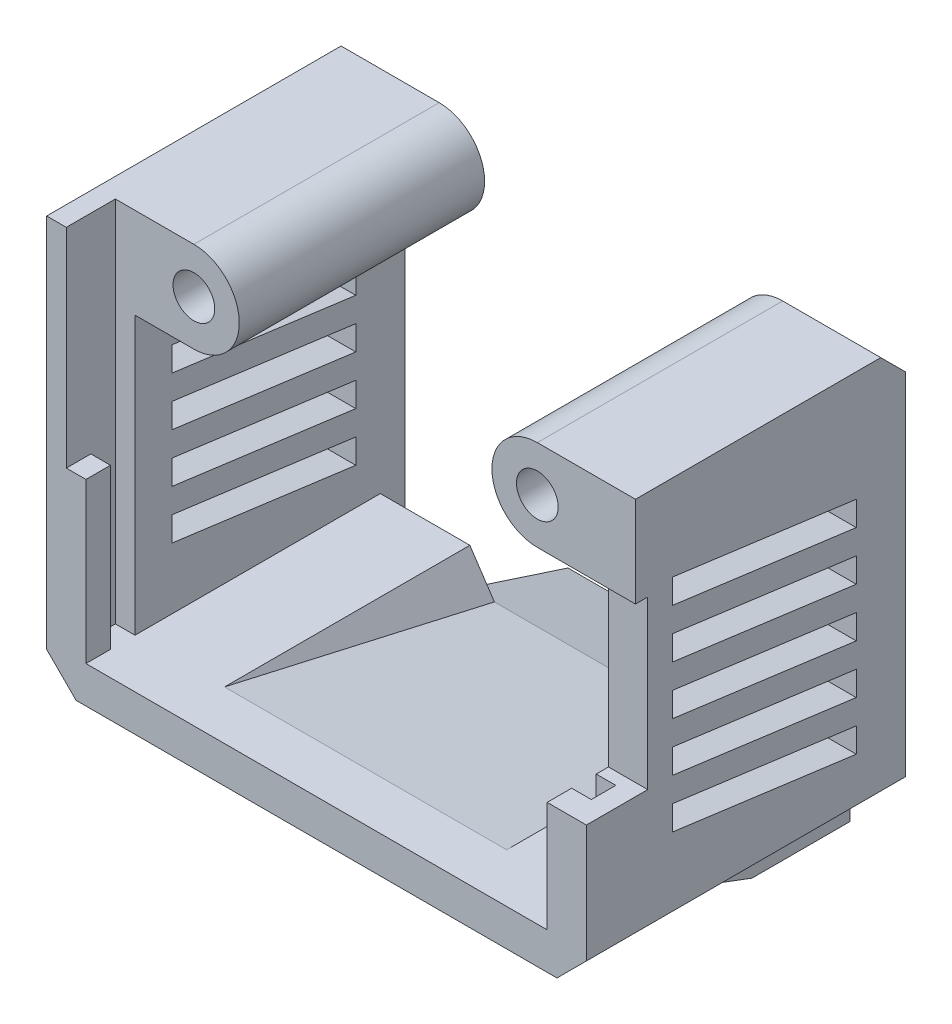
SolidWorks part; units mm, degrees
ref_plane "Спереди" through (0, 0, 0) normal (0, 0, 1) x (1, 0, 0)
ref_plane "Сверху" through (0, 0, 0) normal (0, 1, 0) x (1, 0, 0)
ref_plane "Справа" through (0, 0, 0) normal (1, 0, 0) x (0, 0, -1)
sketch "Эскиз1" plane through (0, 0, 0) normal (0, 0, 1) x (1, 0, 0)
  line L1 (22, 44) -> (-22, 44)
  line L2 (22, 44) -> (22, 10)
  line L3 (22, 10) -> (-22, 10)
  line L4 (-22, 44) -> (-22, 10)
  line L5 (22, 44) -> (-22, 10) construction
  line L6 (22, 10) -> (-22, 44) construction
  point P0 (0, 27)
  dimension "D1" = 10
  dimension "D2" = 44
  dimension "D3" = 44
extrude "Бобышка-Вытянуть1" add sketch "Эскиз1" along normal blind 24
sketch "Эскиз2" plane through (0, 44, 0) normal (0, 1, 0) x (1, 0, 0)
  line L0 (0, 0) -> (0, -24) construction
  line L1 (22, 0) -> (-22, 0) construction
  line L2 (-18.8, 0) -> (18.8, 0)
  line L3 (-18.8, 0) -> (-18.8, -20)
  line L4 (-20.4, -22) -> (-20.4, -20)
  line L5 (18.8, 0) -> (18.8, -20)
  line L6 (-22, -24) -> (-22, 0) construction
  line L7 (22, -24) -> (-22, -24) construction
  line L8 (-18.8, -24) -> (18.8, -24)
  line L9 (-18.8, -24) -> (-18.8, -22)
  line L10 (-18.8, -20) -> (-20.4, -20)
  line L11 (18.8, -24) -> (18.8, -22)
  line L12 (18.8, -22) -> (20.4, -22)
  line L13 (-18.8, -22) -> (-20.4, -22)
  line L14 (18.8, -20) -> (20.4, -20)
  line L15 (20.4, -22) -> (20.4, -20)
  line L16 (22, -24) -> (22, 0) construction
  point P6 (0, 0)
  point P16 (0, -24)
  dimension "D1" = 1.6
  dimension "D2" = 3.2
  dimension "D3" = 2
  dimension "D4" = 20
extrude "Вырез-Вытянуть1" cut sketch "Эскиз2" against normal blind 31
sketch "Эскиз5" plane through (0, 0, 0) normal (0, 0, -1) x (-1, 0, 0)
  line L0 (22, 10) -> (-22, 10) construction
  line L1 (-11.5, 10) -> (11.5, 10)
  line L2 (-11.5, 10) -> (-11.5, 1)
  line L3 (-11.5, 1) -> (11.5, 1)
  line L4 (11.5, 10) -> (11.5, 1)
  point P6 (0, 1)
  dimension "D1" = 23
  dimension "D2" = 9
extrude "Бобышка-Вытянуть4" add sketch "Эскиз5" along normal blind 8 separate body
sketch "Эскиз6" plane through (11.5, 0, 0) normal (1, 0, 0) x (0, 0, -1)
  line L0 (0, 1) -> (-24, 10)
  line L1 (-24, 10) -> (0, 10)
  line L2 (0, 10) -> (0, 1)
extrude "Бобышка-Вытянуть5" add sketch "Эскиз6" against normal up to surface (23 mm away) up to face at (-11.5, 5.5, -4)
sketch "Эскиз7" plane through (-11.5, 0, 0) normal (-1, 0, 0) x (0, 0, 1)
  line L0 (-8, 1) -> (0, 1) construction
  line L3 (0, 44) -> (0, 10) construction
  circle A0 centre (-4.5, 5) radius 1.8
  dimension "D1" = 3.6
  dimension "D2" = 4
  dimension "D3" = 4.5
extrude "Вырез-Вытянуть2" cut sketch "Эскиз7" against normal up to surface (23 mm away) up to face at (11.5, 6.4, 1.6)
ref_plane "Плоскость1" through (-9.5, 0, 0) normal (-1, 0, 0) x (0, 0, 1)
sketch "Эскиз8" plane through (-9.5, 0, 0) normal (-1, 0, 0) x (0, 0, 1)
  line L0 (0, 10) -> (20, 13)
  line L1 (20, 13) -> (0, 13)
  line L2 (0, 13) -> (0, 10)
extrude "Вырез-Вытянуть4" cut sketch "Эскиз8" against normal offset from surface (19 mm away) 2 up to face at (11.5, 6.8, -4.5)
sketch "Эскиз9" plane through (-11.5, 0, 0) normal (-1, 0, 0) x (0, 0, 1)
  line L0 (0, 10) -> (-8, 7.4)
  line L1 (-8, 7.4) -> (-8, 10)
  line L2 (-8, 10) -> (0, 10)
  circle A0 centre (-4.5, 5) radius 1.8 construction
  dimension "D1" = 2.4
extrude "Вырез-Вытянуть6" cut sketch "Эскиз9" against normal up to surface (23 mm away) up to face at (11.5, 6.8, -4.5)
chamfer "Фаска2" distance 2 distance2 3 2 edges at (-9.5, 13, 10) (9.5, 13, 10) first distance on face at (0, 13, 16)
sketch "Эскиз11" plane through (0, 0, 0) normal (0, 0, -1) x (-1, 0, 0)
  line L0 (-22, 44) -> (-18.8, 44) construction
  line L1 (-14, 43) -> (-18.8, 43)
  line L2 (-18.8, 13) -> (-18.8, 44) construction
  line L3 (-18.8, 43) -> (-18.8, 35.6)
  line L4 (-18.8, 35.6) -> (-14, 35.6)
  line L5 (0, 0) -> (0, 30) construction
  line L6 (18.8, 35.6) -> (14, 35.6)
  line L7 (18.8, 43) -> (18.8, 35.6)
  line L8 (14, 43) -> (18.8, 43)
  circle A0 centre (-14, 39.3) radius 1.7
  arc A1 (-14, 35.6) -> (-14, 43) centre (-14, 39.3) ccw
  arc A2 (14, 35.6) -> (14, 43) centre (14, 39.3) cw
  circle A3 centre (-14, 39.3) radius 3.7 construction
  circle A4 centre (14, 39.3) radius 1.7
  point P11 (-10.3, 30)
  dimension "D1" = 14
  dimension "D3" = 3.4
  dimension "D2" = 4.7
  dimension "D4" = 2
extrude "Бобышка-Вытянуть6" add sketch "Эскиз11" against normal up to surface (20 mm away) up to face at (19.6, 28.5, 20)
sketch "Эскиз13" plane through (-22, 0, 0) normal (-1, 0, 0) x (0, 0, 1)
  line L0 (0, 44) -> (0, 10) construction
  line L1 (2, 34) -> (17, 36)
  line L2 (2, 34) -> (2, 32)
  line L3 (2, 32) -> (17, 34)
  line L4 (17, 36) -> (17, 34)
  line L5 (24, 44) -> (0, 44) construction
  line L6 (0, 14) -> (24, 14) construction
  line L7 (24, 44) -> (24, 10) construction
  line L8 (2, 30) -> (17, 32)
  line L9 (2, 30) -> (2, 28)
  line L10 (2, 28) -> (17, 30)
  line L11 (17, 32) -> (17, 30)
  line L12 (2, 26) -> (17, 28)
  line L13 (2, 26) -> (2, 24)
  line L14 (2, 24) -> (17, 26)
  line L15 (17, 28) -> (17, 26)
  line L16 (2, 22) -> (17, 24)
  line L17 (2, 22) -> (2, 20)
  line L18 (2, 20) -> (17, 22)
  line L19 (17, 24) -> (17, 22)
  line L20 (2, 18) -> (17, 20)
  line L21 (2, 18) -> (2, 16)
  line L22 (2, 16) -> (17, 18)
  line L23 (17, 20) -> (17, 18)
  dimension "D1" = 2
  dimension "D2" = 15
  dimension "D3" = 2
  dimension "D4" = 10
  dimension "D5" = 8
  dimension "D6" = 30
  dimension "D7" = 5
extrude "Вырез-Вытянуть7" cut sketch "Эскиз13" against normal blind 4
mirror "Зеркальное отражение1" about plane through (0, 0, 0) normal (1, 0, 0) of "Вырез-Вытянуть7"
chamfer "Фаска3" distance 2.4 angle 45 2 edges at (-22, 10, 12) (22, 10, 12)
sketch "Эскиз14" plane through (0, 44, 0) normal (0, 1, 0) x (1, 0, 0)
  line L0 (22, -24) -> (18.8, -24) construction
  line L1 (-20.4, -20) -> (20.4, -20)
  line L2 (-20.4, -20) -> (-20.4, -24)
  line L3 (-20.4, -24) -> (20.4, -24)
  line L4 (20.4, -20) -> (20.4, -24)
extrude "Вырез-Вытянуть8" cut sketch "Эскиз14" against normal blind 18
sketch "Эскиз15" plane through (0, 0, 0) normal (0, 0, -1) x (-1, 0, 0)
  line L0 (-22, 12.4) -> (-22, 44) construction
  line L1 (-22, 43) -> (22, 43)
  line L2 (-22, 43) -> (-22, 44)
  line L3 (-22, 44) -> (22, 44)
  line L4 (22, 43) -> (22, 44)
  line L5 (18.8, 44) -> (22, 44) construction
extrude "Вырез-Вытянуть9" cut sketch "Эскиз15" against normal up to surface (24 mm away) up to face at (0, 23.175, 24)
sketch "Эскиз16" plane through (0, 0, 24) normal (0, 0, 1) x (1, 0, 0)
  line L0 (18.8, 13) -> (18.8, 26) construction
  line L1 (18.8, 22) -> (22, 22)
  line L2 (18.8, 22) -> (18.8, 35.6)
  line L3 (18.8, 35.6) -> (22, 35.6)
  line L4 (22, 22) -> (22, 35.6)
  line L5 (22, 12.4) -> (22, 43) construction
  line L6 (11.5, 10) -> (19.6, 10) construction
  line L7 (14, 35.6) -> (18.8, 35.6) construction
  point P10 (15.55, 10)
  dimension "D1" = 12
extrude "Вырез-Вытянуть10" cut sketch "Эскиз16" against normal blind 5
sketch "Эскиз17" plane through (0, 43, 0) normal (0, 1, 0) x (1, 0, 0)
  line L1 (20.4, -20) -> (22, -20)
  line L2 (20.4, -20) -> (20.4, -24)
  line L3 (20.4, -24) -> (22, -24)
  line L4 (22, -20) -> (22, -24)
extrude "Вырез-Вытянуть11" cut sketch "Эскиз17" against normal up to surface (7.4 mm away) up to face at (18.6667, 35.6, 15.6667)
sketch "Эскиз18" plane through (0, 0, 0) normal (0, 0, -1) x (-1, 0, 0)
  line L1 (-18.8, 13) -> (-18.8, 35.6) construction
  line L2 (0, 0) -> (0, 13) construction
  line L3 (-11.5, 13) -> (11.5, 13) construction
  line L4 (-22, 43) -> (-18.8, 43)
  line L7 (-22, 43) -> (-22, 12.4)
  line L8 (-19.6, 10) -> (-18.8, 10)
  line L9 (-18.8, 43) -> (-18.8, 10)
  line L10 (-11.5, 10) -> (-19.6, 10) construction
  line L11 (-22, 12.4) -> (-19.6, 10)
  line L12 (22, 12.4) -> (19.6, 10)
  line L13 (18.8, 43) -> (18.8, 10)
  line L14 (19.6, 10) -> (18.8, 10)
  line L15 (22, 43) -> (22, 12.4)
  line L16 (22, 43) -> (18.8, 43)
extrude "Бобышка-Вытянуть7" add sketch "Эскиз18" along normal blind 2
chamfer "Фаска4" distance 2 angle 45 2 edges at (-20.4, 43, -2) (20.4, 43, -2)
